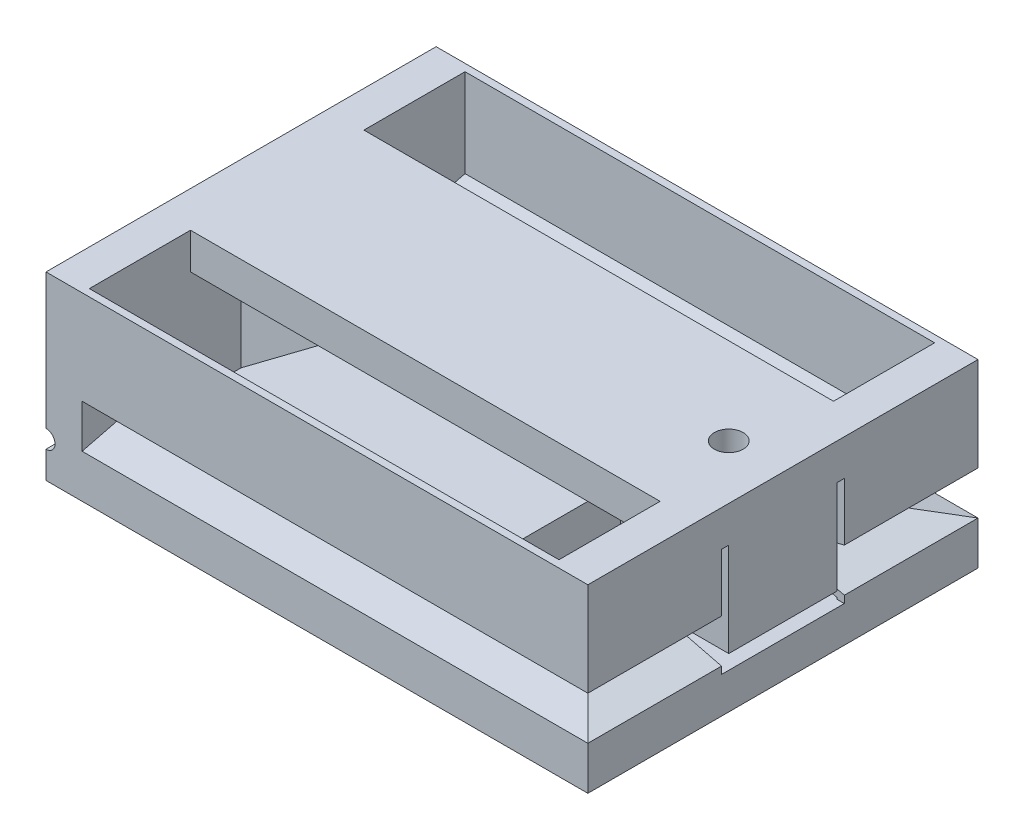
SolidWorks part; units mm, degrees
ref_plane "Front Plane" through (0, 0, 0) normal (0, 0, 1) x (1, 0, 0)
ref_plane "Top Plane" through (0, 0, 0) normal (0, 1, 0) x (1, 0, 0)
ref_plane "Right Plane" through (0, 0, 0) normal (1, 0, 0) x (0, 0, -1)
sketch "Sketch1" plane through (0, 0, 0) normal (0, 0, 1) x (1, 0, 0)
  line L0 (0, 0) -> (7, 0)
  line L1 (0, 0) -> (0, -1.5)
  line L2 (0, -1.5) -> (7, -1.5)
  line L3 (7, 0) -> (7, 0.5)
  line L4 (7, 0.5) -> (-0.5, 0.5)
  line L5 (-0.5, 0.5) -> (-0.5, -2)
  line L6 (-0.5, -2) -> (7, -2)
  line L7 (7, -2) -> (7, -1.5)
  dimension "D1" = 7
  dimension "D2" = 1.5
  dimension "D3" = 0.5
  dimension "D4" = 0.5
  dimension "0.5" = 0.5
extrude "Base shape" add sketch "Sketch1" along normal blind 2.7 and the other way blind 2.7
sketch "Sketch12" plane through (0, 0, 0) normal (0, 0, 1) x (1, 0, 0)
  line L0 (0, 0) -> (2, 0)
  line L1 (0, 0) -> (7, 0) construction
  line L2 (2, 0) -> (0, -1.5)
  line L3 (0, -1.5) -> (0, 0)
  dimension "D1" = 2
extrude "Hinge stabilizer" add sketch "Sketch12" along normal blind 0.5 and the other way blind 0.5
sketch "Sketch2" plane through (0, 0.5, 0) normal (0, 1, 0) x (1, 0, 0)
  line L0 (7, -2.7) -> (7, 2.7) construction
  line L1 (5.5, -0.75) -> (7, -0.75)
  line L2 (5.5, -0.75) -> (5.5, 0.75)
  line L3 (5.5, 0.75) -> (7, 0.75)
  line L4 (7, -0.75) -> (7, 0.75)
  line L5 (5.5, -0.75) -> (7, 0.75) construction
  line L6 (5.5, 0.75) -> (7, -0.75) construction
  point P0 (6.25, 0)
  point P7 (7, 0)
  dimension "D1" = 1.5
extrude "Drive screw housing" add sketch "Sketch2" against normal blind 1.8
sketch "Sketch4" plane through (0, -1.3, 0) normal (0, -1, 0) x (1, 0, 0)
  line L0 (7, 0.75) -> (7, -0.75) construction
  line L1 (5.5, 0.75) -> (7, 0.75) construction
  circle A0 centre (6.25, 0) radius 0.2
  point P4 (7, 0)
  point P7 (6.25, 0.75)
  dimension "D1" = 0.4
extrude "screw thread" cut sketch "Sketch4" against normal blind 11.5
sketch "Sketch5" plane through (0, 0.5, 0) normal (0, 1, 0) x (1, 0, 0)
  line L0 (-0.5, -2.7) -> (-0.5, 2.7) construction
  line L1 (0, 2.7) -> (6.5, 2.7)
  line L2 (0, 2.7) -> (0, 1.2)
  line L3 (0, 1.2) -> (6.5, 1.2)
  line L4 (6.5, 2.7) -> (6.5, 1.2)
  line L5 (0, -1.2) -> (6.5, -1.2)
  line L6 (0, -1.2) -> (0, -2.7)
  line L7 (0, -2.7) -> (6.5, -2.7)
  line L8 (6.5, -1.2) -> (6.5, -2.7)
  line L9 (7, -2.7) -> (7, 2.7) construction
  line L10 (7, 2.7) -> (-0.5, 2.7) construction
  line L11 (7, -2.7) -> (-0.5, -2.7) construction
  dimension "D1" = 0.5
  dimension "D2" = 0.5
  dimension "D3" = 0
  dimension "D4" = 0
  dimension "D5" = 1.5
extrude "goldpin/loading cutout" cut sketch "Sketch5" against normal blind 1.5
sketch "Sketch6" plane through (0, -2, 0) normal (0, -1, 0) x (1, 0, 0)
  line L0 (7, 2.7) -> (7, -2.7) construction
  line L1 (4, 0.75) -> (5.5, 0.75)
  line L2 (4, 0.75) -> (4, -0.75)
  line L3 (4, -0.75) -> (5.5, -0.75)
  line L4 (5.5, 0.75) -> (5.5, -0.75)
  line L5 (4, 0.75) -> (5.5, -0.75) construction
  line L6 (4, -0.75) -> (5.5, 0.75) construction
  line L7 (7, -2.7) -> (7, 2.7) construction
  point P0 (4.75, 0)
  point P7 (7, 0)
  dimension "D1" = 1.5
  dimension "D2" = 1.5
extrude "Trodes exit" cut sketch "Sketch6" against normal blind 0.5
sketch "Sketch10" plane through (0, 0, 2.7) normal (0, 0, 1) x (1, 0, 0)
  line L0 (-0.5, 0.5) -> (-0.5, -2) construction
  circle A0 centre (-0.5, -1.5) radius 0.125
  dimension "D2" = 0.25
  dimension "D1" = 0.5
extrude "Back hinge" cut sketch "Sketch10" against normal through all
sketch "Sketch13" plane through (0, 0, 0) normal (1, 0, 0) x (0, 0, -1)
  line L0 (-0.75, 0) -> (-0.75, -0.3008)
  line L1 (-0.75, -1.3) -> (-0.75, 0) construction
  line L2 (-0.75, -0.3008) -> (0, -0.7)
  line L3 (0, -0.7) -> (0.75, -0.3008)
  line L4 (0.75, -1.3) -> (0.75, 0) construction
  line L5 (0.75, -0.3008) -> (0.75, 0)
  line L6 (0.75, 0) -> (-0.75, 0)
  dimension "D1" = 0.7
extrude "Boss-Extrude1" add sketch "Sketch13" along normal blind 5.5
sketch "Sketch7" plane through (0, 0, 2.7) normal (0, 0, 1) x (1, 0, 0)
  line L1 (6.9, 0) -> (6.9, -0.7219)
  line L30 (7, 0) -> (7, -0.8)
  line L39 (7, -1.3) -> (7, 0) construction
  line L40 (7, -0.8) -> (5.8, -1.1)
  line L41 (5.8, -1.1) -> (7, -1.4)
  line L42 (7, -1.4) -> (7, -1.5)
  line L43 (6.9, -0.7219) -> (5.3877, -1.1)
  line L44 (5.3877, -1.1) -> (6.9, -1.4781)
  line L45 (6.9, -1.4781) -> (6.9, -1.5)
  arc A0 (7, 0) -> (6.9, 0) centre (6.95, 0) ccw
  arc A1 (7, -1.5) -> (6.9, -1.5) centre (6.95, -1.5) cw
  point P5 (7, -1.4119)
  point P9 (0, 0)
  dimension "D1" = 1.2
  dimension "D2" = 0.3
  dimension "D3" = 0.1
  dimension "D4" = 0.8
  dimension "D5" = 0.1
extrude "Front bellow" add sketch "Sketch7" against normal offset from surface (1.85 mm away) 0.85 up to plane "Front Plane"
sketch "Sketch15" plane through (0, 0, 0) normal (1, 0, 0) x (0, 0, -1)
  line L0 (-2.7, 0.5) -> (-2.7, -0.8)
  line L1 (-2.7, -0.8) -> (-1.5, -1.1)
  line L2 (-0.85, -1.1) -> (-2.7, -1.1) construction
  line L3 (-1.5, -1.1) -> (-2.7, -1.4)
  line L4 (-2.7, -1.4) -> (-2.7, -2)
  line L5 (-2.7, 0.5) -> (-3.0212, -1.1)
  line L6 (-3.0212, -1.1) -> (-2.7, -2)
  dimension "D1" = 1.2
extrude "Cut-Extrude1" cut sketch "Sketch15" along normal through all
sketch "Sketch16" plane through (0, 0, 0) normal (1, 0, 0) x (0, 0, -1)
  line L0 (-2.7, 0.5) -> (-2.7, -0.8)
  line L1 (-2.7, -0.8) -> (-1.5, -1.1)
  line L2 (-1.5, -1.1) -> (-2.7, -1.4)
  line L3 (-2.7, -1.4) -> (-2.7, -2)
  line L4 (-2.6, 0.5) -> (-2.6, -0.7219)
  line L5 (-2.6, -0.7219) -> (-1.0877, -1.1)
  line L6 (-1.0877, -1.1) -> (-2.6, -1.4781)
  line L7 (-2.6, -1.4781) -> (-2.6, -2)
  line L8 (-2.7, 0.5) -> (-2.6, 0.5)
  line L9 (-2.7, -2) -> (-2.6, -2)
  dimension "D1" = 0.1
extrude "Boss-Extrude2" add sketch "Sketch16" along normal up to body from surface separate body starting at face at (0, -0.3418, 1.2875)
mirror "Mirror1" about plane through (0, 0, 0) normal (0, 0, 1) of "Cut-Extrude1", "Boss-Extrude2", "Front bellow"
